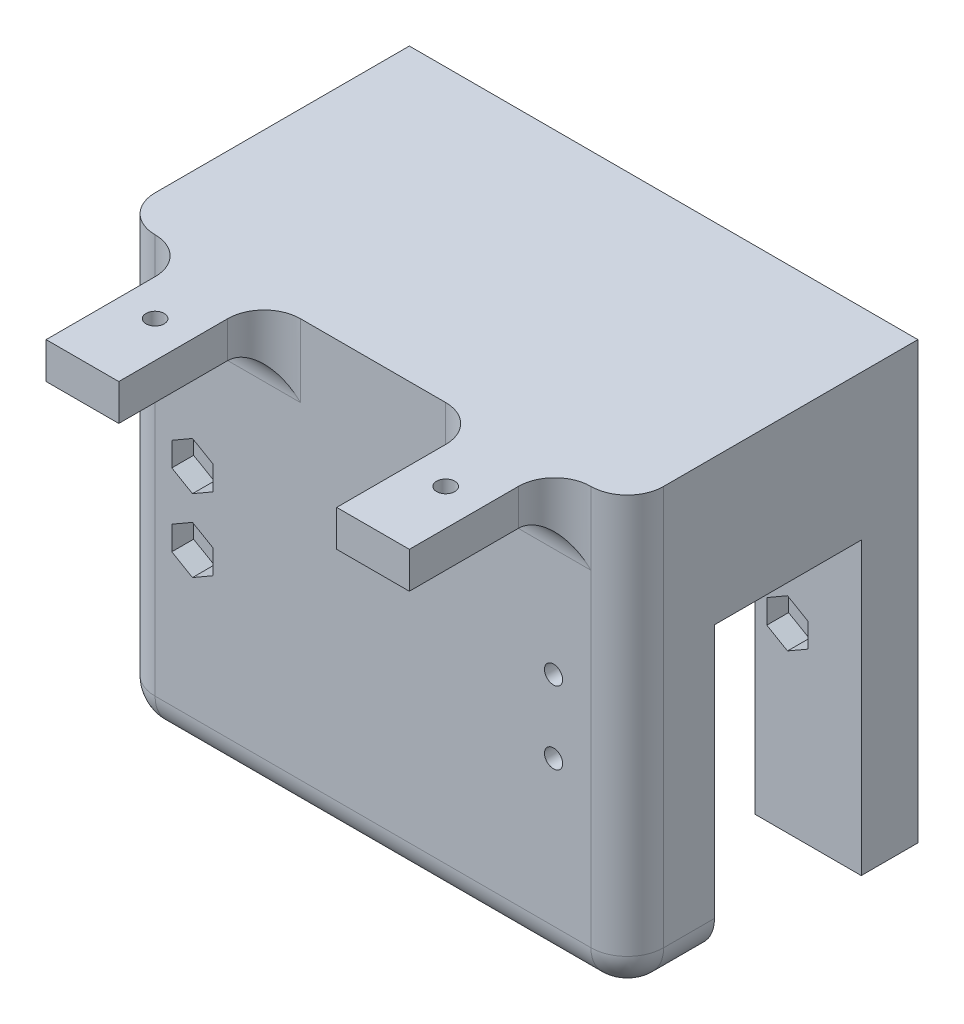
SolidWorks part; units mm, degrees
ref_plane "正面" through (0, 0, 0) normal (0, 0, 1) x (1, 0, 0)
ref_plane "平面" through (0, 0, 0) normal (0, 1, 0) x (1, 0, 0)
ref_plane "右側面" through (0, 0, 0) normal (1, 0, 0) x (0, 0, -1)
sketch "ｽｹｯﾁ2" plane through (0, 0, 0) normal (0, 0, 1) x (1, 0, 0)
  line L1 (-35, 30) -> (35, 30)
  line L2 (-35, 30) -> (-35, -30)
  line L3 (-35, -30) -> (35, -30)
  line L4 (35, 30) -> (35, -30)
  line L5 (-35, 30) -> (35, -30) construction
  line L6 (-35, -30) -> (35, 30) construction
  line L11 (-1.1602, 0.9945) -> (26.8884, -23.0472) construction
  line L12 (-15.8388, -9.5033) -> (15.8388, 9.5033) construction
  point P0 (0, 0)
  point P6 (0, 0)
  dimension "D1" = 70
  dimension "D2" = 60
extrude "ﾎﾞｽ - 押し出し2" add sketch "ｽｹｯﾁ2" along normal blind 40
sketch "ｽｹｯﾁ3" plane through (0, 0, 0) normal (0, 0, 1) x (1, 0, 0)
  line L1 (-20.35, 10.25) -> (20.35, 10.25)
  line L2 (-20.35, 10.25) -> (-20.35, -10.25)
  line L3 (-20.35, -10.25) -> (20.35, -10.25)
  line L4 (20.35, 10.25) -> (20.35, -10.25)
  line L5 (-20.35, 10.25) -> (20.35, -10.25) construction
  line L6 (-20.35, -10.25) -> (20.35, 10.25) construction
  point P0 (0, 0)
  dimension "D1" = 40.7
  dimension "D2" = 20.5
extrude "ｶｯﾄ - 押し出し1" cut sketch "ｽｹｯﾁ3" along normal blind 28 contours L2 L1 L4 L3
sketch "ｽｹｯﾁ4" plane through (0, 0, 0) normal (0, 0, 1) x (1, 0, 0)
  line L0 (20.35, 10.25) -> (35, 10.25)
  line L1 (35, -30) -> (35, 30) construction
  line L2 (35, 10.25) -> (35, -10.25)
  line L3 (35, -10.25) -> (20.35, -10.25)
  line L4 (20.35, -10.25) -> (20.35, 10.25)
extrude "ﾎﾞｽ - 押し出し3" add sketch "ｽｹｯﾁ4" along normal blind 28
sketch "ｽｹｯﾁ5" plane through (0, 0, 0) normal (0, 0, 1) x (1, 0, 0)
  line L0 (20.35, 10.25) -> (35, 10.25)
  line L1 (35, -30) -> (35, 30) construction
  line L2 (35, 10.25) -> (35, -10.25)
  line L3 (35, -10.25) -> (20.35, -10.25)
  line L4 (20.35, -10.25) -> (20.35, 10.25)
sketch "ｽｹｯﾁ6" plane through (0, 0, 0) normal (0, 0, 1) x (1, 0, 0)
  line L0 (-25, -30) -> (-25, -25)
  line L1 (-35, -30) -> (35, -30) construction
  line L2 (-25, -25) -> (-15, -25)
  line L3 (-15, -25) -> (-15, -30)
  line L4 (-15, -30) -> (-25, -30)
  line L5 (15, -25) -> (15, -30)
  line L6 (15, -30) -> (25, -30)
  line L7 (25, -30) -> (25, -25)
  line L8 (25, -25) -> (15, -25)
  dimension "D1" = 15
  dimension "D2" = 10
  dimension "D3" = 15
  dimension "D4" = 10
  dimension "D5" = 5
  dimension "D6" = 5
sketch "ｽｹｯﾁ8" plane through (0, 0, 0) normal (0, 0, 1) x (1, 0, 0)
  line L0 (-25, 30) -> (-25, 25)
  line L1 (35, 30) -> (-35, 30) construction
  line L2 (-25, 25) -> (-15, 25)
  line L3 (-15, 25) -> (-15, 30)
  line L4 (-15, 30) -> (-25, 30)
  line L5 (15, 30) -> (15, 25)
  line L6 (15, 25) -> (25, 25)
  line L7 (25, 25) -> (25, 30)
  line L8 (25, 30) -> (15, 30)
  dimension "D1" = 15
  dimension "D2" = 10
  dimension "D3" = 5
  dimension "D4" = 5
  dimension "D5" = 10
  dimension "D6" = 10
  dimension "D7" = 15
extrude "ﾎﾞｽ - 押し出し5" add sketch "ｽｹｯﾁ8" along normal blind 60
sketch "ｽｹｯﾁ15" plane through (0, 0, 0) normal (0, 0, 1) x (1, 0, 0)
  line L0 (-20.35, 10.25) -> (-20.35, -30)
  line L1 (-15, -30) -> (-25, -30) construction
  line L2 (-20.35, -30) -> (20.35, -30)
  line L3 (15, -30) -> (25, -30) construction
  line L4 (20.35, -30) -> (20.35, 10.25)
  line L5 (20.35, 10.25) -> (-20.35, 10.25)
extrude "ｶｯﾄ - 押し出し6" cut sketch "ｽｹｯﾁ15" along normal blind 28
ref_plane "平面1" through (0, -30, 0) normal (0, -1, 0) x (-1, 0, 0)
sketch "ｽｹｯﾁ16" plane through (0, -30, 0) normal (0, -1, 0) x (-1, 0, 0)
  line L0 (-20.35, -28) -> (-35, -28)
  line L1 (-35, -40) -> (-35, 0) construction
  line L2 (-35, -28) -> (-35, -7.7959)
  line L3 (-35, -7.7959) -> (-20.35, -7.7959)
  line L4 (-20.35, -28) -> (-20.35, 0) construction
  line L5 (-20.35, -7.7959) -> (-20.35, -28)
extrude "ｶｯﾄ - 押し出し7" cut sketch "ｽｹｯﾁ16" against normal blind 40
hole_wizard "M3x0.5 ねじ穴1" positions "ｽｹｯﾁ9" profile "ｽｹｯﾁ10" tap size "M3x0.5" standard "JIS" end condition through all
sketch "ｽｹｯﾁ9" plane through (0, 30, 0) normal (0, 1, 0) x (1, 0, 0)
  line L1 (15, -40) -> (-15, -40) construction
  line L2 (35, -40) -> (25, -40) construction
  point P0 (-20, -50)
  point P2 (20, -50)
  dimension "D1" = 10
  dimension "D2" = 10
  dimension "D3" = 20
  dimension "D4" = 20
sketch "ｽｹｯﾁ10" plane through (-20, 30, 50) normal (1, 0, 0) x (0, 0, 1)
  line L0 (0, 0) -> (0, 60)
  line L1 (0, 60) -> (1.25, 60)
  line L2 (1.25, 60) -> (1.25, 0)
  line L5 (1.25, 0) -> (0, 0)
  line L11 (0, -6.35) -> (0, 107.95) construction
  dimension "次ｻｰﾌｪｽまでのねじ下穴ﾄﾞﾘﾙ直径" = 2.5
  dimension "次ｻｰﾌｪｽまでのねじ下穴ﾄﾞﾘﾙの深さ" = 60
cosmetic thread "穴のねじ山1" parameters "D2"=3
cosmetic thread "穴のねじ山2" parameters "D2"=3
fillet "ﾌｨﾚｯﾄ1" radius 5 6 edges at (-25, 27.5, 40) (15, 27.5, 40) (-15, 27.5, 40) (25, 27.5, 40) (20, 25, 40) (-20, 25, 40)
fillet "ﾌｨﾚｯﾄ2" radius 5 4 edges at (35, 0, 40) (35, -30, 34) (0, -30, 40) (-35, 0, 40)
fillet "ﾌｨﾚｯﾄ3" radius 5 2 edges at (-33.5355, -28.5355, 38.5355) (-35, -30, 17.5)
hole_wizard "M3x0.5 ねじ穴2" positions "ｽｹｯﾁ12" profile "ｽｹｯﾁ13" tap size "M3x0.5" standard "JIS" end condition through all
sketch "ｽｹｯﾁ12" plane through (0, 0, 0) normal (0, 0, -1) x (-1, 0, 0)
  line L0 (20.35, 10.25) -> (20.35, -30) construction
  point P0 (24.85, 5)
  point P2 (24.85, -5)
  dimension "D1" = 10
  dimension "D2" = 5
  dimension "D3" = 24.85
  dimension "D4" = 4.5
sketch "ｽｹｯﾁ13" plane through (-24.85, 5, 0) normal (1, 0, 0) x (0, 1, 0)
  line L0 (0, 0) -> (0, 60)
  line L1 (0, 60) -> (1.25, 60)
  line L2 (1.25, 60) -> (1.25, 0)
  line L5 (1.25, 0) -> (0, 0)
  line L11 (0, -6.35) -> (0, 107.95) construction
  dimension "次ｻｰﾌｪｽまでのねじ下穴ﾄﾞﾘﾙ直径" = 2.5
  dimension "次ｻｰﾌｪｽまでのねじ下穴ﾄﾞﾘﾙの深さ" = 60
cosmetic thread "穴のねじ山3" parameters "D2"=3
cosmetic thread "穴のねじ山4" parameters "D2"=3
mirror "ﾐﾗｰ1" about plane through (0, 0, 0) normal (1, 0, 0) of "M3x0.5 ねじ穴2"
cosmetic thread "穴のねじ山5" parameters "D2"=3
cosmetic thread "穴のねじ山6" parameters "D2"=3
sketch "ｽｹｯﾁ17" plane through (0, 0, 40) normal (0, 0, 1) x (1, 0, 0)
  line L0 (-24.85, 5) -> (-24.85, -5) construction
  line L2 (-24.85, 8.2909) -> (-27.7, 6.6454)
  line L3 (-27.7, 6.6454) -> (-27.7, 3.3546)
  line L4 (-27.7, 3.3546) -> (-24.85, 1.7091)
  line L5 (-24.85, 1.7091) -> (-22, 3.3546)
  line L6 (-22, 3.3546) -> (-22, 6.6454)
  line L7 (-22, 6.6454) -> (-24.85, 8.2909)
  line L8 (-22, -6.6454) -> (-22, -3.3546)
  line L9 (-22, -3.3546) -> (-24.85, -1.7091)
  line L10 (-24.85, -1.7091) -> (-27.7, -3.3546)
  line L11 (-27.7, -3.3546) -> (-27.7, -6.6454)
  line L12 (-27.7, -6.6454) -> (-24.85, -8.2909)
  line L13 (-24.85, -8.2909) -> (-22, -6.6454)
  circle A0 centre (-24.85, 5) radius 2.85 construction
  circle A1 centre (-24.85, -5) radius 2.85 construction
  dimension "D1" = 5.7
  dimension "5.7" = 5.7
extrude "ｶｯﾄ - 押し出し8" cut sketch "ｽｹｯﾁ17" against normal blind 3
sketch "ｽｹｯﾁ18" plane through (0, 0, 7.7959) normal (0, 0, 1) x (1, 0, 0)
  line L0 (24.85, -5) -> (24.85, 5) construction
  line L2 (27.7, 3.3546) -> (27.7, 6.6454)
  line L3 (27.7, 6.6454) -> (24.85, 8.2909)
  line L4 (24.85, 8.2909) -> (22, 6.6454)
  line L5 (22, 6.6454) -> (22, 3.3546)
  line L6 (22, 3.3546) -> (24.85, 1.7091)
  line L7 (24.85, 1.7091) -> (27.7, 3.3546)
  line L8 (27.7, -6.6454) -> (27.7, -3.3546)
  line L9 (27.7, -3.3546) -> (24.85, -1.7091)
  line L10 (24.85, -1.7091) -> (22, -3.3546)
  line L11 (22, -3.3546) -> (22, -6.6454)
  line L12 (22, -6.6454) -> (24.85, -8.2909)
  line L13 (24.85, -8.2909) -> (27.7, -6.6454)
  circle A0 centre (24.85, 5) radius 2.85 construction
  circle A1 centre (24.85, -5) radius 2.85 construction
  dimension "D1" = 5.7
  dimension "D2" = 5.7
extrude "ｶｯﾄ - 押し出し9" cut sketch "ｽｹｯﾁ18" against normal blind 3
ref_plane "平面2" through (0, 0, 20) normal (0, 0, -1) x (-1, 0, 0)
sketch "ｽｹｯﾁ19" plane through (0, 0, 20) normal (0, 0, -1) x (-1, 0, 0)
  line L0 (24.85, -5) -> (24.85, 5) construction
  line L1 (24.85, 1.7091) -> (35, 1.7091)
  line L2 (24.85, 1.7091) -> (27.7, 3.3546)
  line L3 (27.7, 3.3546) -> (27.7, 6.6454)
  line L4 (27.7, 6.6454) -> (24.85, 8.2909)
  line L5 (24.85, 8.2909) -> (22, 6.6454)
  line L6 (22, 6.6454) -> (22, 3.3546)
  line L7 (22, 3.3546) -> (24.85, 1.7091)
  line L8 (27.7, -6.6454) -> (27.7, -3.3546)
  line L9 (27.7, -3.3546) -> (24.85, -1.7091)
  line L10 (24.85, -1.7091) -> (22, -3.3546)
  line L11 (22, -3.3546) -> (22, -6.6454)
  line L12 (22, -6.6454) -> (24.85, -8.2909)
  line L13 (24.85, -8.2909) -> (27.7, -6.6454)
  line L14 (35, 30) -> (35, -25) construction
  line L15 (35, 1.7091) -> (35, 8.2909)
  line L16 (35, 8.2909) -> (24.85, 8.2909)
  line L17 (24.85, -1.7091) -> (35, -1.7091)
  line L18 (35, -1.7091) -> (35, -8.2909)
  line L19 (35, -8.2909) -> (24.85, -8.2909)
  circle A0 centre (24.85, 5) radius 2.85 construction
  circle A1 centre (24.85, -5) radius 2.85 construction
  dimension "D1" = 5.7
  dimension "D2" = 5.7
extrude "ｶｯﾄ - 押し出し10" cut sketch "ｽｹｯﾁ19" against normal blind 6 contours L15 L16 L4 L3 L2 L1 | L6 L7 L2 L3 L4 L5 | L12 L13 L8 L9 L10 L11 | L19 L18 L17 L9 L8 L13
